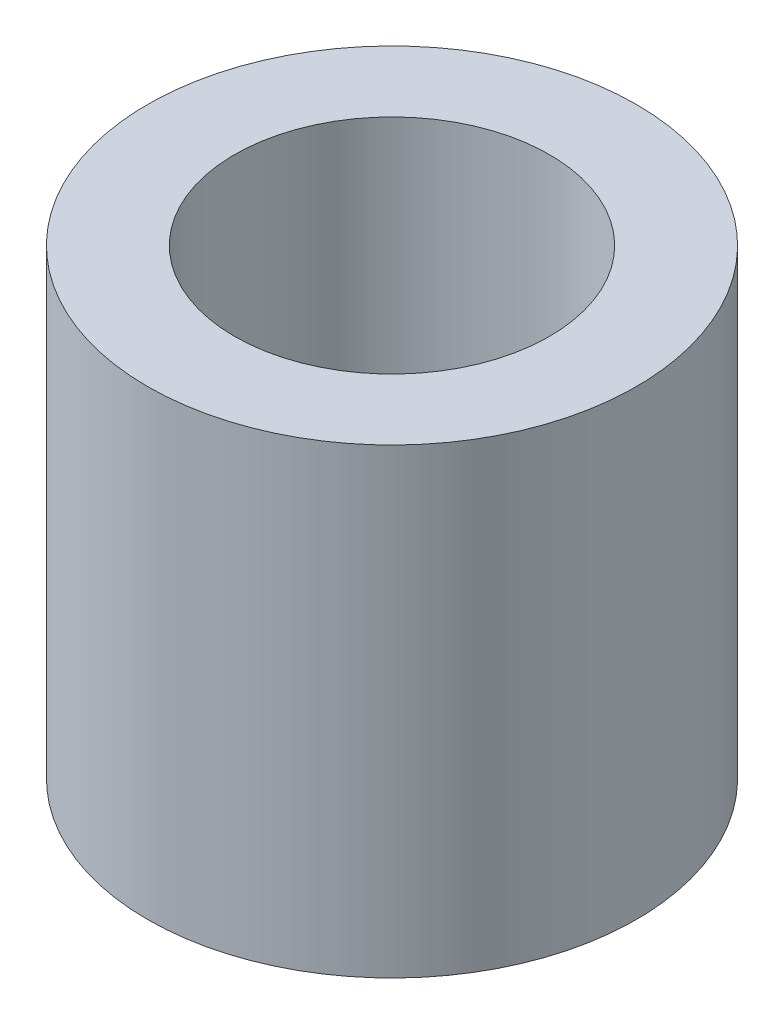
SolidWorks part; units mm, degrees
material "ABS"
ref_plane "Front Plane" through (0, 0, 0) normal (0, 0, 1) x (1, 0, 0)
ref_plane "Top Plane" through (0, 0, 0) normal (0, 1, 0) x (1, 0, 0)
ref_plane "Right Plane" through (0, 0, 0) normal (1, 0, 0) x (0, 0, -1)
sketch "Sketch1" plane through (0, 0, 0) normal (0, 1, 0) x (1, 0, 0)
  circle A1 centre (0, 0) radius 2.25
  dimension "D2" = 4.5
extrude "Boss-Extrude1" add sketch "Sketch1" along normal blind 4.25
sketch "Sketch2" plane through (0, 4.25, 0) normal (0, 1, 0) x (1, 0, 0)
  point P0 (0, 0)
hole_wizard "M2.5 Clearance Hole1" positions "Sketch2" profile "Sketch3" hole size "M2.5" standard "ANSI Metric" end condition through all
sketch "Sketch3" plane through (0, 4.25, 0) normal (1, 0, 0) x (0, 0, 1)
  line L0 (0, 0) -> (0, 4.25)
  line L1 (0, 4.25) -> (1.45, 4.25)
  line L2 (1.45, 4.25) -> (1.45, 0)
  line L5 (1.45, 0) -> (0, 0)
  line L11 (0, -6.35) -> (0, 107.95) construction
  dimension "Thru Hole Dia." = 2.9
  dimension "Thru Hole Depth" = 4.25
